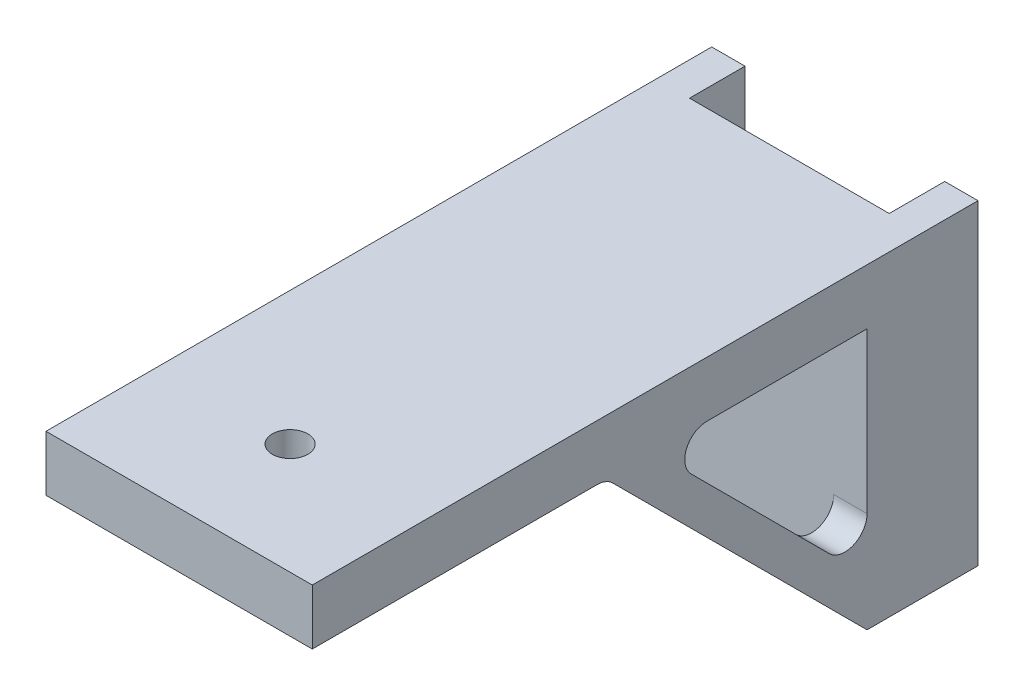
SolidWorks part; units mm, degrees
ref_plane "Front Plane" through (0, 0, 0) normal (0, 0, 1) x (1, 0, 0)
ref_plane "Top Plane" through (0, 0, 0) normal (0, 1, 0) x (1, 0, 0)
ref_plane "Right Plane" through (0, 0, 0) normal (1, 0, 0) x (0, 0, -1)
sketch "Sketch1" plane through (0, 0, 0) normal (0, 0, 1) x (1, 0, 0)
  line L1 (-9, -8.5) -> (9, -8.5) construction
  line L2 (-9, -8.5) -> (-9, 8.5)
  line L3 (-9, 8.5) -> (9, 8.5)
  line L4 (9, -8.5) -> (9, 8.5)
  line L5 (-9, -8.5) -> (9, 8.5) construction
  line L6 (-9, 8.5) -> (9, -8.5) construction
  line L7 (-9, -8.5) -> (9, -8.5) construction
  line L8 (-9, -8.5) -> (-9, -20)
  line L9 (-9, -20) -> (9, -20)
  line L10 (9, -8.5) -> (9, -20)
  line L11 (-9, -8.5) -> (9, -20) construction
  line L12 (-9, -20) -> (9, -8.5) construction
  circle A0 centre (0, 0) radius 1.6
  point P0 (0, 0)
  point P10 (0, -14.25)
  dimension "D3" = 3.2
  dimension "D1" = 18
  dimension "D2" = 17
  dimension "D4" = 11.5
extrude "Boss-Extrude1" add sketch "Sketch1" along normal blind 5
sketch "Sketch2" plane through (0, 0, 5) normal (0, 0, 1) x (1, 0, 0)
  line L0 (-9, -20) -> (9, -20) construction
  line L1 (9, 8.5) -> (12, 8.5)
  line L2 (9, 8.5) -> (9, -20)
  line L3 (9, -20) -> (12, -20)
  line L4 (12, 8.5) -> (12, -20)
  line L5 (-9, 8.5) -> (-12, 8.5)
  line L6 (-9, 8.5) -> (-9, -20)
  line L7 (-9, -20) -> (-12, -20)
  line L8 (-12, 8.5) -> (-12, -20)
  line L9 (-9, -20) -> (9, -20)
  line M9 (9, -20) -> (9, 8.5)
  line M11 (-9, 8.5) -> (-9, -20)
  dimension "D1" = 3
extrude "Boss-Extrude2" add sketch "Sketch2" against normal blind 10 contours L5 L8 L7 M11 | L4 L1 L3 M9 region at (-10.5, -5.75, 5) region at (10.5, -5.75, 5)
sketch "Sketch3" plane through (0, 8.5, 0) normal (0, 1, 0) x (1, 0, 0)
  line L1 (-12, -5) -> (12, -5)
  line L2 (-12, -5) -> (-12, -55)
  line L3 (-12, -55) -> (12, -55)
  line L4 (12, -5) -> (12, -55)
  circle A0 centre (0, -45) radius 1.6
  point P9 (0, -5)
  dimension "D2" = 3.2
  dimension "D1" = 50
  dimension "D3" = 40
extrude "Boss-Extrude3" add sketch "Sketch3" against normal blind 5
sketch "Sketch4" plane through (-12, 0, 0) normal (-1, 0, 0) x (0, 0, 1)
  line L0 (5, 3.5) -> (55, 3.5) construction
  line L2 (5, 3.5) -> (55, 3.5)
  line L3 (5, 3.5) -> (5, -20) construction
  line L4 (5, -20) -> (28.5, 3.5)
  line L5 (5, 3.5) -> (5, -20)
  line L6 (24.2574, 3.5) -> (5, -15.7574)
  line M12 (5, -20) -> (5, 3.5)
  dimension "D1" = 45
  dimension "D2" = 3
extrude "Boss-Extrude4" add sketch "Sketch4" against normal blind 3 contours L2 L6 L4 M12 region at (-12, -7.2244, 15.7244)
extrude "Boss-Extrude5" add sketch "Sketch4<3>" along normal blind 3 from surface contours L2 L6 L4 M12 region at (-12, -7.2244, 15.7244) starting at face at (12, -2.6667, 18.3333)
sketch "Sketch4<3>" plane through (-12, 0, 0) normal (-1, 0, 0) x (0, 0, 1) same geometry as "Sketch4"
sketch "Sketch5" plane through (0, 0, 5) normal (0, 0, 1) x (1, 0, 0)
  line L0 (-5, 2.8868) -> (-5, -2.8868)
  line L1 (0, -3.4641) -> (3, -1.7321)
  line L2 (3, -1.7321) -> (3, 1.7321)
  line L3 (3, 1.7321) -> (0, 3.4641)
  line L4 (0, 3.4641) -> (-3, 1.7321)
  line L5 (-3, 1.7321) -> (-3, -1.7321)
  line L6 (-3, -1.7321) -> (0, -3.4641)
  line L13 (-5, -2.8868) -> (0, -5.7735)
  line L14 (0, -5.7735) -> (5, -2.8868)
  line L15 (5, -2.8868) -> (5, 2.8868)
  line L16 (5, 2.8868) -> (0, 5.7735) construction
  line L17 (0, 5.7735) -> (-5, 2.8868) construction
  line L18 (12, 3.5) -> (-12, 3.5) construction
  line L19 (12, 3.5) -> (-12, 3.5)
  line L20 (-5, 2.8868) -> (-5, 3.5)
  line L21 (5, 2.8868) -> (5, 3.5)
  circle A0 centre (0, 0) radius 1.6 construction
  circle A1 centre (0, 0) radius 1.6
  circle A2 centre (0, 0) radius 3 construction
  dimension "D1" = 6
  dimension "D2" = 2
extrude "Boss-Extrude6" add sketch "Sketch5" along normal blind 2.4 contours L15 L21 L19 L20 L0 L13 L14 L6 L5 L4 L3 L2 L1 region at (-4.8636, 3.1934, 5)
fillet "Fillet1" radius 2 6 edges at (10.5, -15.7574, 5) (10.5, 3.5, 24.2574) (-10.5, -15.7574, 5) (-10.5, 3.5, 24.2574) (10.5, 3.5, 28.5) (-10.5, 3.5, 28.5)
